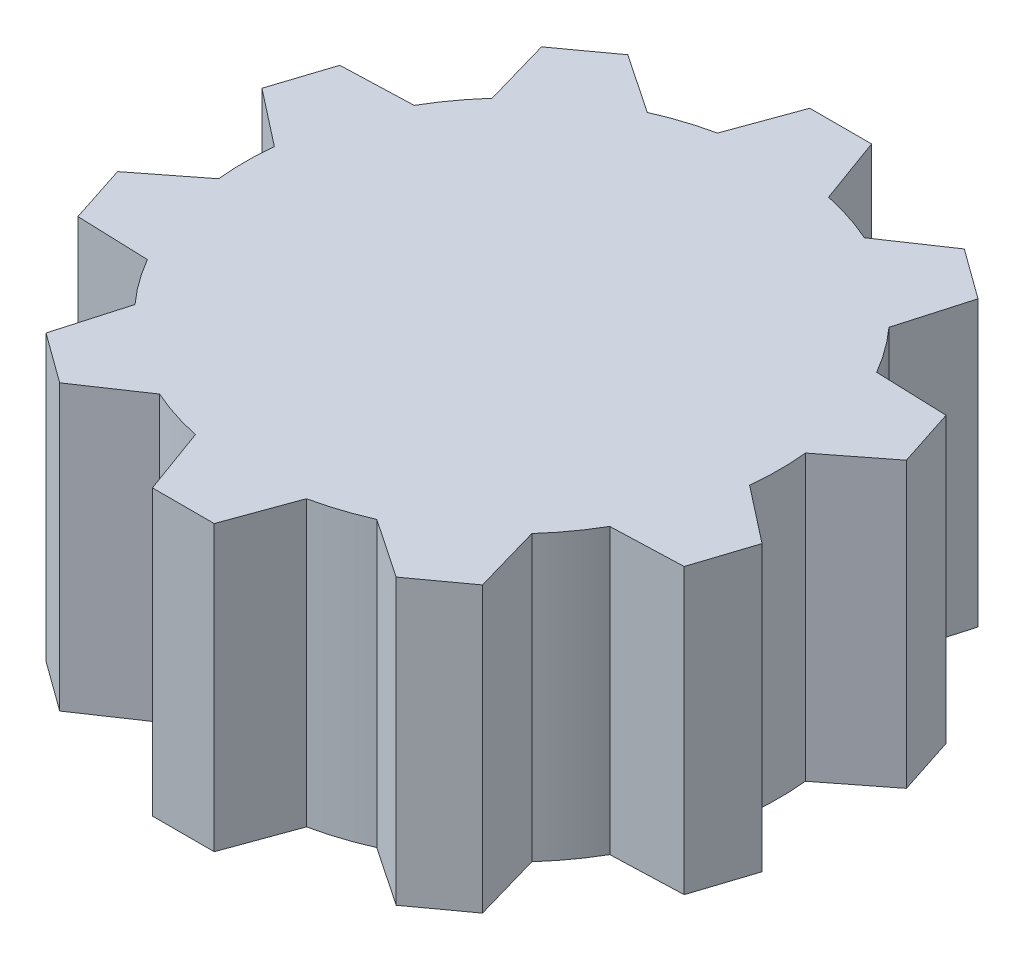
SolidWorks part; units mm, degrees
note: The reader was unsure of these and kept them because the rebuilt part matched: shared geometry of "Croquis1<4>", "Croquis1<5>", "Croquis1<7>", "Croquis1<10>".
ref_plane "Front Plane" through (0, 0, 0) normal (0, 0, 1) x (1, 0, 0)
ref_plane "Top Plane" through (0, 0, 0) normal (0, 1, 0) x (1, 0, 0)
ref_plane "Right Plane" through (0, 0, 0) normal (1, 0, 0) x (0, 0, -1)
sketch "Croquis1" plane through (0, 0, 0) normal (0, 1, 0) x (1, 0, 0)
  line L0 (-1.2517, 13.2996) -> (1.2483, 13.3004)
  line L1 (-1.2517, 13.2996) -> (-2.2476, 10.5635)
  line L2 (1.2483, 13.3004) -> (2.2441, 10.5643)
  line L3 (-0.0017, 13.3) -> (0, 7) construction
  line L4 (6.8046, 11.4954) -> (8.8276, 10.0265)
  line L5 (8.8276, 10.0265) -> (8.0251, 7.2276)
  line L6 (6.8046, 11.4954) -> (4.3907, 9.8672)
  line L7 (12.2619, 5.3003) -> (13.0351, 2.9229)
  line L8 (13.0351, 2.9229) -> (10.7407, 1.1303)
  line L9 (12.2619, 5.3003) -> (9.352, 5.4019)
  line L10 (13.0355, -2.9193) -> (12.2637, -5.2972)
  line L11 (12.2637, -5.2972) -> (9.3538, -5.3988)
  line L12 (13.0355, -2.9193) -> (10.7411, -1.1267)
  line L13 (8.83, -10.0239) -> (6.8079, -11.4939)
  line L14 (6.8079, -11.4939) -> (4.394, -9.8657)
  line L15 (8.83, -10.0239) -> (8.0274, -7.225)
  line L16 (1.2517, -13.2996) -> (-1.2483, -13.3004)
  line L17 (-1.2483, -13.3004) -> (-2.2441, -10.5643)
  line L18 (1.2517, -13.2996) -> (2.2476, -10.5635)
  line L19 (-6.8046, -11.4954) -> (-8.8276, -10.0265)
  line L20 (-8.8276, -10.0265) -> (-8.0251, -7.2276)
  line L21 (-6.8046, -11.4954) -> (-4.3907, -9.8672)
  line L22 (-12.2619, -5.3003) -> (-13.0351, -2.9229)
  line L23 (-13.0351, -2.9229) -> (-10.7407, -1.1303)
  line L24 (-12.2619, -5.3003) -> (-9.352, -5.4019)
  line L25 (-13.0355, 2.9193) -> (-12.2637, 5.2972)
  line L26 (-12.2637, 5.2972) -> (-9.3538, 5.3988)
  line L27 (-13.0355, 2.9193) -> (-10.7411, 1.1267)
  line L28 (-8.83, 10.0239) -> (-6.8079, 11.4939)
  line L29 (-6.8079, 11.4939) -> (-4.394, 9.8657)
  line L30 (0, -7) -> (0, 7) construction
  line L31 (-3.2517, 4.75) -> (3.2482, 4.75)
  line L32 (-3.7275, -0.4102) -> (-2.7372, -9.41)
  line L33 (2.7372, -9.41) -> (3.7275, -0.4102)
  line L34 (-3.7277, 0.4087) -> (-2.7409, 9.4089)
  line L35 (-8.83, 10.0239) -> (-8.0274, 7.225)
  line L37 (-3.25, -4.75) -> (3.25, -4.75)
  line L38 (2.7335, 9.4111) -> (3.7273, 0.4116)
  line L39 (6.8046, 11.4954) -> (8.8276, 10.0265) [skipped]
  line L40 (-8.83, 10.0239) -> (-6.8079, 11.4939) [skipped]
  circle A0 centre (0, 0) radius 10.8
  arc A4 (-2.7372, -9.41) -> (2.7372, -9.41) centre (0, 0) ccw
  arc A5 (2.7335, 9.4111) -> (-2.7409, 9.4089) centre (0, 0) ccw
  circle A6 centre (0, 0) radius 1.6
  circle A7 centre (0, 0) radius 2.6
  circle A8 centre (0, 0) radius 3.75
  circle A9 centre (0, -7) radius 1.1
  circle A10 centre (0, 7) radius 1.1
  point P47 (0, 0)
  point P48 (0, 0)
  point P55 (-0.0017, 13.3)
  point P56 (-0.0017, 4.75)
  point P58 (0, 0)
  point P65 (0, -4.75)
  point P69 (0, 0)
  point P72 (0, 0)
  point P74 (0, -9.8)
  dimension "D3" = 12.559
  dimension "D4" = 21.6
  dimension "D5" = 3.2
  dimension "D6" = 5.2
  dimension "D7" = 7.5
  dimension "D12" = 19.6
  dimension "D13" = 6.3
  dimension "D9" = 4.75
  dimension "D14" = 2.2
  dimension "D15" = 2.2
  dimension "D2" = 40
  dimension "D8" = 9.5
  dimension "D10" = 6.4999
  dimension "D11" = 14
  dimension "D16" = 0.9959
  dimension "D17" = 0.9959
  dimension "D18" = 10
extrude "Saliente-Extruir1" add sketch "Croquis1" along normal blind 11.5
extrude "Cortar-Extruir1" cut sketch "Croquis1<4>" along normal blind 1.7 contours A8 L32 L37 L33 | L32 A4 L33 L37 A9 | A8 L38 L31 L34 | L38 A5 L34 L31 A10 | A10 | A9
sketch "Croquis1<4>" plane through (0, 0, 0) normal (0, 1, 0) x (1, 0, 0) same geometry as "Croquis1"
extrude "Cortar-Extruir2" cut sketch "Croquis1<5>" along normal blind 1.2 from surface at 1.7 contours A8 L38 L31 L34 | A8 L32 L37 L33
sketch "Croquis1<5>" plane through (0, 0, 0) normal (0, 1, 0) x (1, 0, 0) same geometry as "Croquis1"
sketch "Croquis2" plane through (0, 0, 0) normal (1, 0, 0) x (0, 0, -1)
  line L0 (0, -3.7522) -> (0, 15.3042) construction
extrude "Cut-Extrude1" cut sketch "Croquis1<7>" along normal blind 6.5 from surface at 1.7 starting at face at (0, 1.7, 7.1775)
sketch "Croquis1<7>" plane through (0, 0, 0) normal (0, 1, 0) x (1, 0, 0) same geometry as "Croquis1"
extrude "Boss-Extrude1" add sketch "Croquis1<10>" against normal blind 5.6 from surface at 11.5 contours L30 A6 | A6 L30 | A7 L30 A6 | L30 A7 A6 | L30 A8 A7 | A8 L30 A7 starting at face at (0, 11.5, 3.75)
sketch "Croquis1<10>" plane through (0, 0, 0) normal (0, 1, 0) x (1, 0, 0) same geometry as "Croquis1"
